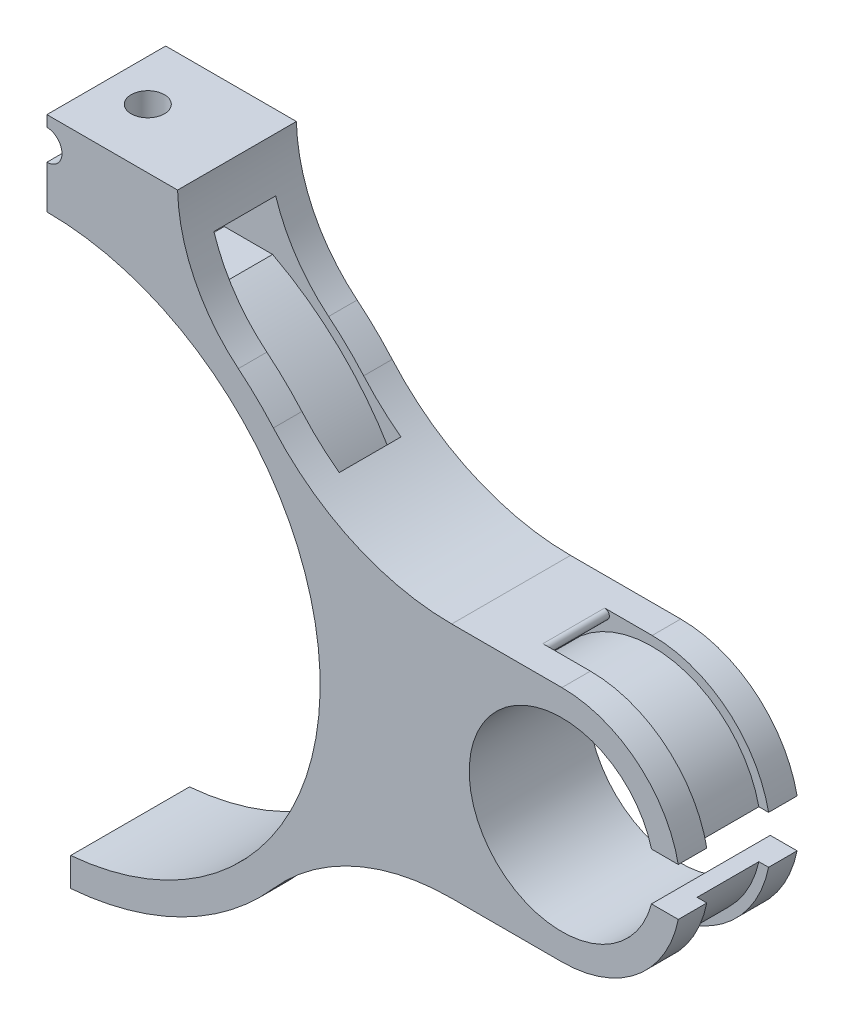
SolidWorks part; units mm, degrees
ref_plane "Front Plane" through (0, 0, 0) normal (0, 0, 1) x (1, 0, 0)
ref_plane "Top Plane" through (0, 0, 0) normal (0, 1, 0) x (1, 0, 0)
ref_plane "Right Plane" through (0, 0, 0) normal (1, 0, 0) x (0, 0, -1)
sketch "Sketch1" plane through (0, 0, 0) normal (0, 0, 1) x (1, 0, 0)
  circle A0 centre (0, 0) radius 57.5
  circle A1 centre (0, 0) radius 63.5
  dimension "D1" = 115
  dimension "D2" = 6
extrude "main shape" add sketch "Sketch1" along normal mid plane 25
sketch "Sketch6" plane through (0, 0, 0) normal (0, 0, 1) x (1, 0, 0)
  line L0 (-58.3717, 25) -> (-58.3717, -25) construction
  line L1 (-58.3717, 25) -> (-108.3717, 25)
  line L2 (-58.3717, -25) -> (-108.3717, -25)
  circle A0 centre (0, 0) radius 63.5 construction
  arc A1 (-108.3717, 25) -> (-108.3717, -25) centre (-108.3717, 0) ccw
  circle A3 centre (0, 0) radius 63.5
  arc A4 (-58.3717, 25) -> (-58.3717, -25) centre (0, 0) ccw
  dimension "D2" = 50
  dimension "D3" = 50
  dimension "D1" = 0
extrude "motor mount" add sketch "Sketch6" along normal up to surface and the other way up to surface up to face at (63.5, 0, 12.5) other way up to face at (63.5, 0, -12.5)
sketch "Sketch11" plane through (0, 0, 0) normal (0, 0, 1) x (1, 0, 0)
  line L0 (27.5, 75.2364) -> (27.5, 57.2364)
  line L1 (-27.5, 57.2364) -> (-27.5, 75.2364)
  line L2 (27.5, 57.2364) -> (-27.5, 57.2364) construction
  line L3 (27.5, 75.2364) -> (-27.5, 75.2364)
  arc A1 (27.5, 57.2364) -> (-27.5, 57.2364) centre (0, 0) ccw
  arc A3 (-58.3717, -25) -> (-58.3717, 25) centre (0, 0) ccw construction
  dimension "D1" = 55
  dimension "D2" = 18
extrude "harness" add sketch "Sketch11" along normal up to surface and the other way up to surface up to face at (-59.1537, 0, 12.5) other way up to face at (-59.1537, 0, -12.5)
fillet "harness fillet" radius 35 2 edges at (27.5, 57.2364, 0) (-27.5, 57.2364, 0)
sketch "Sketch3" plane through (0, 0, 0) normal (0, 0, 1) x (1, 0, 0)
  circle A0 centre (0, 0) radius 61.5
  circle A1 centre (0, 0) radius 65.5
  circle A3 centre (0, 0) radius 63.5 construction
  dimension "D1" = 2
  dimension "D2" = 4
extrude "main slot" cut sketch "Sketch3" against normal mid plane 13
sketch "Sketch8" plane through (0, 0, 0) normal (0, 0, 1) x (1, 0, 0)
  circle A0 centre (-108.3717, 0) radius 19.5
  arc A2 (-108.3717, 25) -> (-108.3717, -25) centre (-108.3717, 0) ccw construction
  dimension "D1" = 39
extrude "motor cut" cut sketch "Sketch8" against normal through all both and the other way through all
sketch "Sketch9" plane through (0, 0, 0) normal (0, 0, 1) x (1, 0, 0)
  circle A4 centre (-108.3717, 0) radius 25
  arc A5 (-108.3717, 25) -> (-108.3717, -25) centre (-108.3717, 0) ccw construction
  circle A6 centre (-108.3717, 0) radius 23
  dimension "D1" = 2
extrude "motor slot" cut sketch "Sketch9" against normal mid plane 13
fillet "motor mount fillet" radius 50 2 edges at (-58.3717, 25, -9.5) (-58.3717, -25, 9.5)
sketch "Sketch17" plane through (0, 0, -12.5) normal (0, 0, -1) x (-1, 0, 0)
  line L0 (127.8717, 0) -> (133.3717, 0) construction
  line L1 (134.0236, 5) -> (134.0236, -5)
  line L2 (127.2197, -5) -> (134.0236, -5)
  line L3 (127.2197, -5) -> (127.2197, 5)
  line L4 (127.2197, 5) -> (134.0236, 5)
  line L6 (127.2197, -5) -> (134.0236, 5) construction
  line L7 (127.2197, 5) -> (134.0236, -5) construction
  circle A0 centre (108.3717, 0) radius 19.5 construction
  arc A1 (108.3717, -25) -> (108.3717, 25) centre (108.3717, 0) ccw construction
  point P7 (130.6217, 0)
  dimension "D1" = 10
extrude "motor keyway" cut sketch "Sketch17" against normal through all
mirror "Mirror" about plane through (0, 0, 0) normal (1, 0, 0) of "motor mount", "main slot", "motor cut", "motor slot", "motor mount fillet", "motor keyway"
sketch "Sketch13" plane through (0, 75.2364, 0) normal (0, 1, 0) x (1, 0, 0)
  line L0 (0, 0) -> (-8.7312, 0) construction
  line L1 (0, 0) -> (8.7313, 0) construction
  circle A0 centre (-8.7312, 0) radius 3.5
  circle A1 centre (8.7313, 0) radius 3.5
  dimension "D1" = 7
  dimension "D2" = 8.7312
extrude "bolt holes" cut sketch "Sketch13" against normal up to next
sketch "Sketch15" plane through (0, 0, 0) normal (0, 1, 0) x (1, 0, 0)
  line L0 (57.5, 12.5) -> (-57.5, 12.5) construction
  line L1 (5, -12.5) -> (-5, -12.5)
  line L2 (5, -12.5) -> (5, 12.5)
  line L3 (5, 12.5) -> (-5, 12.5)
  line L4 (-5, -12.5) -> (-5, 12.5)
  line L5 (5, -12.5) -> (-5, 12.5) construction
  line L6 (5, 12.5) -> (-5, -12.5) construction
  point P0 (0, 0)
  point P7 (0, 12.5)
  dimension "D1" = 10
extrude "main keyway" cut sketch "Sketch15" against normal through all
sketch "Sketch19" plane through (0, 0, 0) normal (1, 0, 0) x (0, 0, -1)
  line L1 (-6.5, 65.5) -> (6.5, 65.5)
  line L2 (-6.5, 65.5) -> (-6.5, 54.5)
  line L3 (-6.5, 54.5) -> (6.5, 54.5)
  line L4 (6.5, 65.5) -> (6.5, 54.5)
  dimension "D1" = 11
extrude "harness cut" cut sketch "Sketch19" against normal through all both and the other way through all
sketch "Sketch22" plane through (0, 0, 12.5) normal (0, 0, 1) x (1, 0, 0)
  line L0 (0, 75.2364) -> (0, 57.5) construction
  line L1 (27.5, 75.2364) -> (-27.5, 75.2364) construction
  arc A0 (5, -57.2822) -> (-5, -57.2822) centre (0, 0) ccw construction
  circle A1 centre (0, 69.7364) radius 3.175
  dimension "D1" = 6.35
  dimension "D2" = 5.5
extrude "Cut-Extrude1" cut sketch "Sketch22" against normal through all
fillet "Fillet1" radius 1 7 edges at (-55.5187, 34.7552, 0) (-108.3717, 25, 0) (-108.3717, -25, 0) (-55.5187, -34.7552, 0) (55.5187, -34.7552, 0) (108.3717, -25, 0) (108.3717, 25, 0)
sketch "Sketch18" plane through (0, 0, 0) normal (1, 0, 0) x (0, 0, -1)
  line L1 (-40.5418, 82.3163) -> (47.369, 82.3163)
  line L2 (-40.5418, 82.3163) -> (-40.5418, -84.8459)
  line L3 (-40.5418, -84.8459) -> (47.369, -84.8459)
  line L4 (47.369, 82.3163) -> (47.369, -84.8459)
extrude "split for printing" cut sketch "Sketch18" against normal through all
